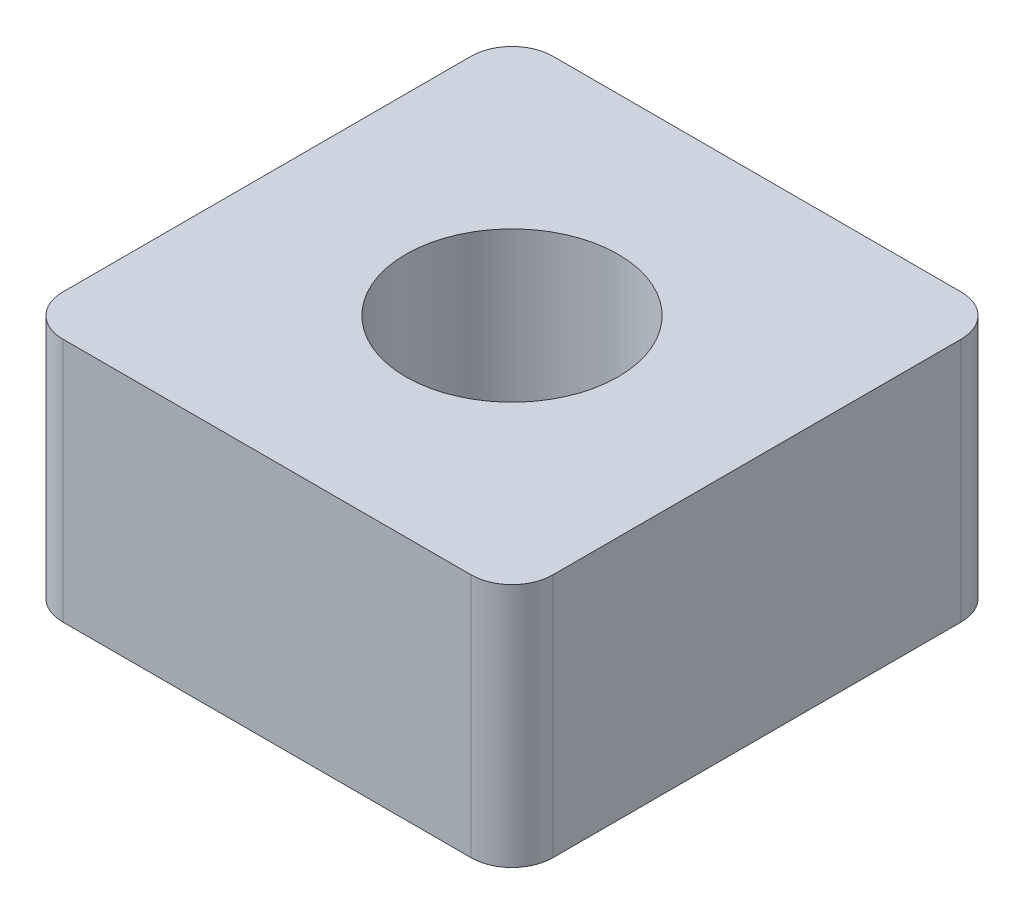
SolidWorks part; units mm, degrees
ref_plane "Front Plane" through (0, 0, 0) normal (0, 0, 1) x (1, 0, 0)
ref_plane "Top Plane" through (0, 0, 0) normal (0, 1, 0) x (1, 0, 0)
ref_plane "Right Plane" through (0, 0, 0) normal (1, 0, 0) x (0, 0, -1)
sketch "Sketch1" plane through (0, 0, 0) normal (0, 1, 0) x (1, 0, 0)
  line L1 (-5, 6) -> (5, 6)
  line L2 (-6, 5) -> (-6, -5)
  line L3 (-5, -6) -> (5, -6)
  line L4 (6, 5) -> (6, -5)
  line L5 (0, -6) -> (0, 6) construction
  line L6 (-6, 0) -> (6, 0) construction
  circle A0 centre (0, 0) radius 2.6
  arc A1 (5, 6) -> (6, 5) centre (5, 5) cw
  arc A2 (6, -5) -> (5, -6) centre (5, -5) cw
  arc A3 (-6, -5) -> (-5, -6) centre (-5, -5) ccw
  arc A4 (-5, 6) -> (-6, 5) centre (-5, 5) ccw
  point P0 (0, 0)
  dimension "D3" = 5.2
  dimension "D4" = 1
  dimension "D1" = 12
  dimension "D2" = 12
extrude "Boss-Extrude1" add sketch "Sketch1" along normal blind 6
